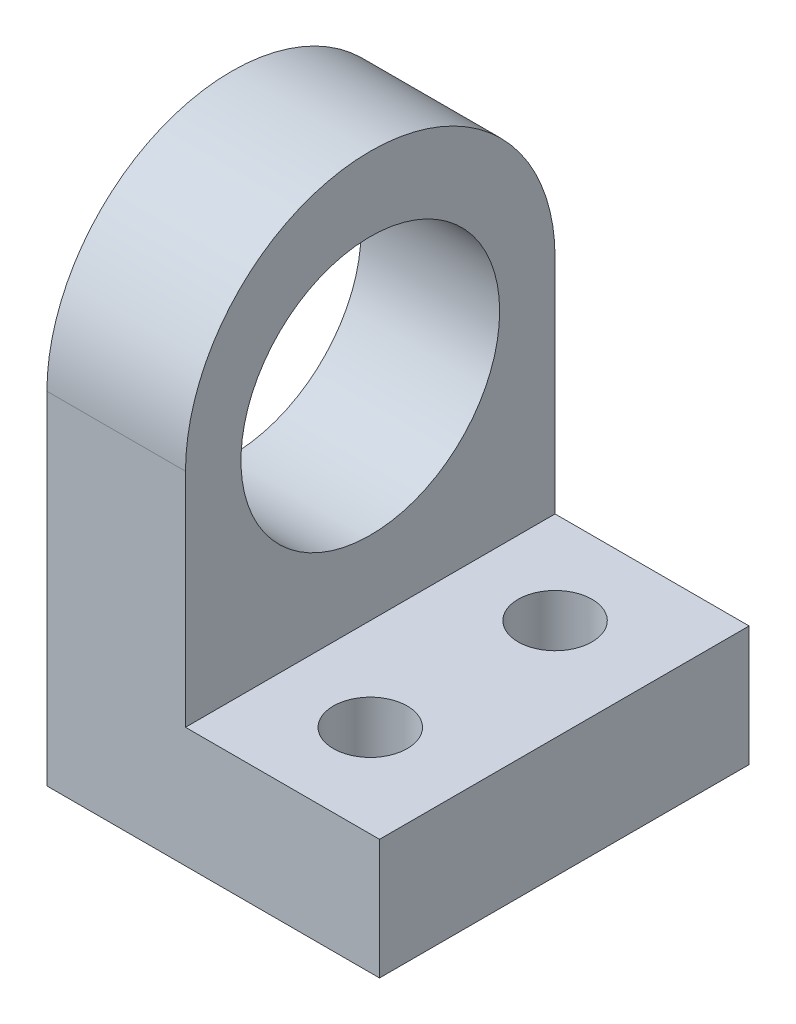
SolidWorks part; units mm, degrees
ref_plane "Front Plane" through (0, 0, 0) normal (0, 0, 1) x (1, 0, 0)
ref_plane "Top Plane" through (0, 0, 0) normal (0, 1, 0) x (1, 0, 0)
ref_plane "Right Plane" through (0, 0, 0) normal (1, 0, 0) x (0, 0, -1)
sketch "Sketch1" plane through (0, 0, 0) normal (0, 0, 1) x (1, 0, 0)
  line L0 (-36, 44) -> (-36, -13)
  line L1 (-36, -13) -> (0, -13)
  line L2 (0, -13) -> (0, 0)
  line L3 (0, 0) -> (-21, 0)
  line L4 (-21, 0) -> (-21, 44)
  line L5 (-21, 44) -> (-36, 44)
  dimension "D1" = 36
  dimension "D2" = 13
  dimension "D3" = 21
  dimension "D4" = 44
extrude "Boss-Extrude5" add sketch "Sketch1" along normal blind 40
fillet "Fillet4" 2 edges at (-28.5, 44, 40) (-28.5, 44, 0) type full round first side face at (-19, 10.3333, 40) second side face at (-19, 10.3333, 0) middle face at (-28.5, 44, 20)
sketch "Sketch8" plane through (-21, 0, 0) normal (1, 0, 0) x (0, 0, -1)
  line L0 (0, 0) -> (0, 24) construction
  circle A0 centre (-20, 22) radius 14
  dimension "D1" = 28
  dimension "D2" = 20
  dimension "D3" = 22
extrude "Cut-Extrude1" cut sketch "Sketch8" against normal blind 40
sketch "Sketch9" plane through (0, 0, 0) normal (0, 1, 0) x (1, 0, 0)
  circle A0 centre (-11, -10) radius 4
  circle A1 centre (-11, -30) radius 4
  point P8 (-61.997, 2.337)
  dimension "D1" = 8
  dimension "D2" = 8
  dimension "D3" = 11
  dimension "D4" = 10
  dimension "11" = 11
  dimension "10" = 10
extrude "Cut-Extrude2" cut sketch "Sketch9" against normal blind 40
